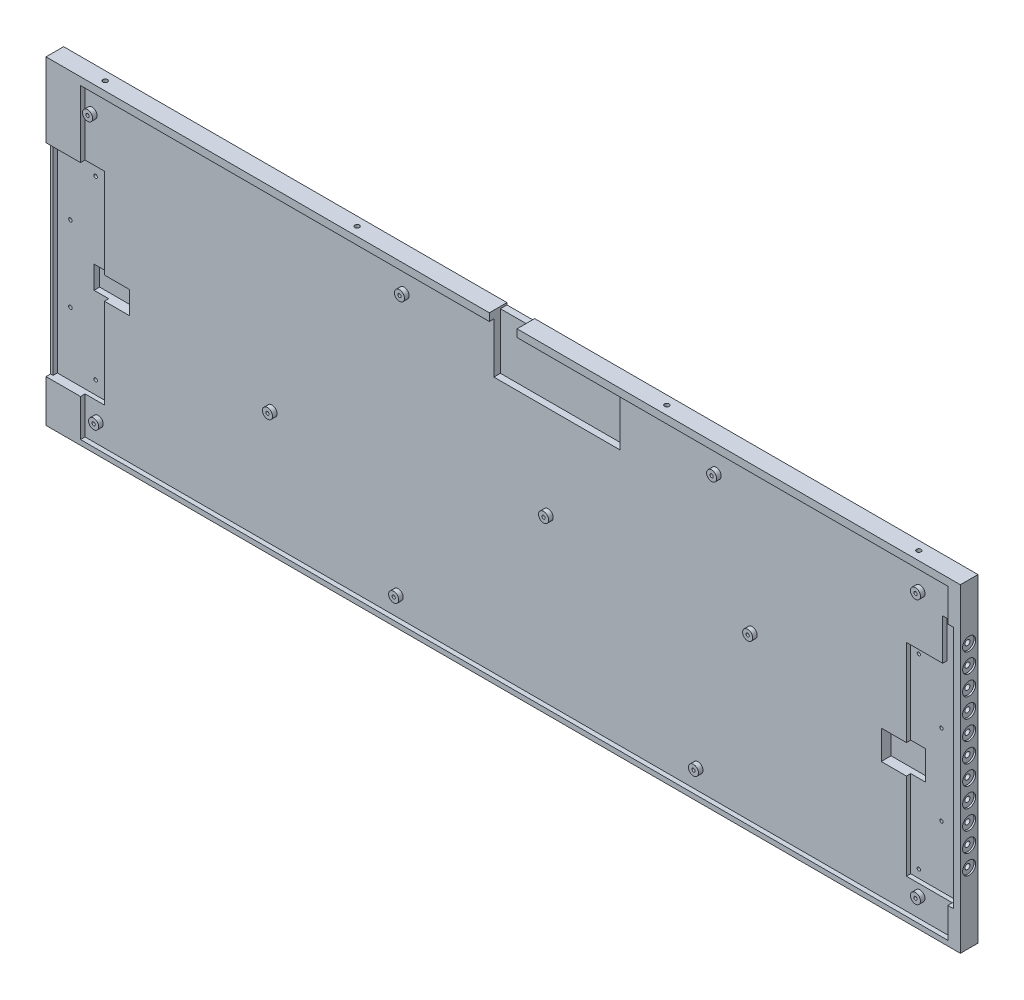
SolidWorks part; units mm, degrees
ref_plane "前视基准面" through (0, 0, 0) normal (0, 0, 1) x (1, 0, 0)
ref_plane "上视基准面" through (0, 0, 0) normal (0, 1, 0) x (1, 0, 0)
ref_plane "右视基准面" through (0, 0, 0) normal (1, 0, 0) x (0, 0, -1)
other "Configuration Table"
sketch "草图1" plane through (0, 0, 0) normal (0, 0, 1) x (1, 0, 0)
  line L1 (0, 0) -> (348.235, 0)
  line L2 (0, 0) -> (0, -124.71)
  line L3 (0, -124.71) -> (348.235, -124.71)
  line L4 (348.235, 0) -> (348.235, -124.71)
  dimension "D1" = 348.235
  dimension "D2" = 124.71
extrude "凸台-拉伸1" add sketch "草图1" along normal blind 7
sketch "草图2" plane through (0, 0, 7) normal (0, 0, 1) x (1, 0, 0)
  line L0 (348.235, 0) -> (0, 0) construction
  line L1 (2, -2) -> (346.235, -2)
  line L2 (2, -2) -> (2, -122.71)
  line L3 (2, -122.71) -> (346.235, -122.71)
  line L4 (346.235, -2) -> (346.235, -122.71)
  line L5 (348.235, -124.71) -> (348.235, 0) construction
  line L6 (0, -124.71) -> (348.235, -124.71) construction
  line L7 (0, 0) -> (0, -124.71) construction
  dimension "D1" = 2
  dimension "D2" = 2
  dimension "D3" = 2
  dimension "D4" = 2
extrude "切除-拉伸1" cut sketch "草图2" against normal blind 1.8
sketch "草图3" plane through (0, 0, 5.2) normal (0, 0, 1) x (1, 0, 0)
  circle A0 centre (4.8, -9.9) radius 2
  circle A1 centre (4.8, -9.9) radius 0.65
  circle A2 centre (7.2, -114.7) radius 2
  circle A3 centre (7.2, -114.7) radius 0.65
  circle A4 centre (76.2, -76.6) radius 2
  circle A5 centre (76.2, -76.6) radius 0.65
  circle A6 centre (128.6, -9.9) radius 2
  circle A7 centre (128.6, -9.9) radius 0.65
  circle A8 centre (126.3, -114.7) radius 2
  circle A9 centre (126.3, -114.7) radius 0.65
  circle A10 centre (185.8, -57.5) radius 2
  circle A11 centre (185.8, -57.5) radius 0.65
  circle A12 centre (252.5, -9.9) radius 2
  circle A13 centre (252.5, -9.9) radius 0.65
  circle A14 centre (245.3, -114.7) radius 2
  circle A15 centre (245.3, -114.7) radius 0.65
  circle A16 centre (333.4, -9.9) radius 2
  circle A17 centre (333.4, -9.9) radius 0.65
  circle A18 centre (333.4, -114.7) radius 2
  circle A19 centre (333.4, -114.7) radius 0.65
  circle A20 centre (266.8, -57.5) radius 2
  circle A21 centre (266.8, -57.5) radius 0.65
  dimension "D1" = 4
  dimension "D2" = 1.3
extrude "凸台-拉伸2" add sketch "草图3" along normal up to surface (1.8 mm away) up to face at (174.1175, -62.355, 7)
sketch "草图4" plane through (0, 0, 5.2) normal (0, 0, 1) x (1, 0, 0)
  line L0 (0, 0) -> (0, -124.71) construction
  line L1 (0, -27.51) -> (9.7, -27.51)
  line L2 (0, -27.51) -> (0, -107.91)
  line L3 (0, -107.91) -> (9.7, -107.91)
  line L4 (9.7, -27.51) -> (9.7, -107.91)
  line L5 (0, -124.71) -> (348.235, -124.71) construction
  dimension "D1" = 80.4
  dimension "D2" = 9.7
  dimension "D3" = 16.8
extrude "切除-拉伸2" cut sketch "草图4" against normal blind 1.7 and the other way through all contours L4 L3 L2 L1
sketch "草图6" plane through (0, 0, 5.2) normal (0, 0, 1) x (1, 0, 0)
  line L5 (3.9, -67.71) -> (9.7, -67.71) construction
  line L6 (3.9, -63.21) -> (19.7, -63.21)
  line L7 (3.9, -63.21) -> (3.9, -72.21)
  line L8 (3.9, -72.21) -> (19.7, -72.21)
  line L9 (19.7, -63.21) -> (19.7, -72.21)
  line L10 (9.7, -27.51) -> (9.7, -107.91) construction
  dimension "D1" = 9
  dimension "D2" = 5.8
  dimension "D3" = 10
extrude "切除-拉伸3" cut sketch "草图6" against normal offset from surface (3.9 mm away) 1.3 up to face at (174.1175, -62.355, 0)
sketch "草图7" plane through (0, 0, 0) normal (-1, 0, 0) x (0, 0, 1)
  line L1 (0, 0) -> (7, 0)
  line L2 (0, 0) -> (0, -27.51)
  line L3 (0, -27.51) -> (7, -27.51)
  line L4 (7, 0) -> (7, -27.51)
  line L5 (7, -107.91) -> (0, -107.91)
  line L6 (7, -107.91) -> (7, -124.71)
  line L7 (7, -124.71) -> (0, -124.71)
  line L8 (0, -107.91) -> (0, -124.71)
  line L9 (0, -107.91) -> (3.5, -107.91)
  line L10 (0, -107.91) -> (0, -27.51)
  line L11 (0, -27.51) -> (3.5, -27.51)
  line L12 (3.5, -107.91) -> (3.5, -27.51)
  line M1 (3.5, -107.91) -> (3.5, -27.51)
  line M2 (3.5, -27.51) -> (7, -27.51)
  line M3 (7, -27.51) -> (7, 0)
  line M4 (7, 0) -> (0, 0)
  line M5 (0, 0) -> (0, -124.71)
  line M6 (0, -124.71) -> (7, -124.71)
  line M7 (7, -124.71) -> (7, -107.91)
  line M8 (7, -107.91) -> (3.5, -107.91)
extrude "凸台-拉伸3" add sketch "草图7" along normal blind 11.7 contours L5 M8 M5 M6 M7 | L5 L3 M1 M5 | L3 M5 M2 M3 M4 region at (0, -13.755, 3.5) region at (0, -67.71, 1.75) region at (0, -116.31, 3.5)
sketch "草图8" plane through (0, 0, 3.5) normal (0, 0, 1) x (1, 0, 0)
  circle A0 centre (-5.5, -82.714) radius 0.7
  circle A1 centre (4.5, -102.714) radius 0.7
  circle A2 centre (-5.5, -52.714) radius 0.7
  circle A3 centre (4.5, -32.714) radius 0.7
  dimension "D1" = 1.4
extrude "切除-拉伸4" cut sketch "草图8" against normal blind 3
sketch "草图9" plane through (0, 0, 3.5) normal (0, 0, 1) x (1, 0, 0)
  line L0 (-11.7, -107.91) -> (2, -107.91) construction
  line L1 (-11.7, -27.51) -> (-10.7, -27.51)
  line L2 (-11.7, -27.51) -> (-11.7, -107.91)
  line L3 (-11.7, -107.91) -> (-10.7, -107.91)
  line L4 (-10.7, -27.51) -> (-10.7, -107.91)
  dimension "D1" = 1
extrude "凸台-拉伸4" add sketch "草图9" along normal up to surface (1.7 mm away) up to face at (64.8892, -65.925, 5.2)
sketch "草图10" plane through (0, 0, 5.2) normal (0, 0, 1) x (1, 0, 0)
  line L1 (328.035, -30.31) -> (348.235, -30.31)
  line L2 (328.035, -30.31) -> (328.035, -110.71)
  line L3 (328.035, -110.71) -> (348.235, -110.71)
  line L4 (348.235, -30.31) -> (348.235, -110.71)
  line L6 (348.235, -124.71) -> (348.235, 0) construction
  line L9 (2, -122.71) -> (346.235, -122.71) construction
  dimension "D1" = 80.4
  dimension "D2" = 20.2
  dimension "D3" = 12
extrude "切除-拉伸5" cut sketch "草图10" against normal blind 1.7 and the other way through all
sketch "草图11" plane through (0, 0, 3.5) normal (0, 0, 1) x (1, 0, 0)
  line L0 (328.035, -70.51) -> (333.835, -70.51) construction
  line L1 (318.035, -64.76) -> (333.835, -64.76)
  line L2 (318.035, -64.76) -> (318.035, -76.26)
  line L3 (318.035, -76.26) -> (333.835, -76.26)
  line L4 (333.835, -64.76) -> (333.835, -76.26)
  line L5 (328.035, -110.71) -> (328.035, -30.31) construction
  dimension "D1" = 11.5
  dimension "D2" = 5.8
  dimension "D3" = 10
extrude "切除-拉伸6" cut sketch "草图11" against normal blind 2.2 and the other way through all
sketch "草图12" plane through (0, 0, 3.5) normal (0, 0, 1) x (1, 0, 0)
  circle A3 centre (331.235, -107.514) radius 0.65
  circle A4 centre (340.235, -86.514) radius 0.65
  circle A5 centre (340.235, -54.514) radius 0.65
  circle A6 centre (331.235, -33.514) radius 0.65
  dimension "D1" = 1.3
extrude "切除-拉伸7" cut sketch "草图12" against normal blind 3
sketch "草图13" plane through (0, 0, 0) normal (0, 0, -1) x (-1, 0, 0)
  line L0 (11.7, -124.71) -> (-348.235, -124.71) construction
  line L1 (-348.235, 0) -> (-351.235, 0)
  line L2 (-348.235, 0) -> (-348.235, -124.71)
  line L3 (-348.235, -124.71) -> (-351.235, -124.71)
  line L4 (-351.235, 0) -> (-351.235, -124.71)
  dimension "D1" = 3
extrude "凸台-拉伸5" add sketch "草图13" against normal up to surface (7 mm away) up to face at (171.1925, -14.955, 7)
sketch "草图14" plane through (0, 0, 5.2) normal (0, 0, 1) x (1, 0, 0)
  line L0 (346.235, -2) -> (2, -2) construction
  line L1 (342.435, -14) -> (348.435, -14)
  line L2 (342.435, -14) -> (342.435, -110.71)
  line L3 (342.435, -110.71) -> (348.435, -110.71)
  line L4 (348.435, -14) -> (348.435, -110.71)
  line L5 (346.235, -110.71) -> (328.035, -110.71) construction
  line L6 (351.235, 0) -> (351.235, -124.71) construction
  dimension "D1" = 12
  dimension "D2" = 6
  dimension "D3" = 2.8
extrude "切除-拉伸8" cut sketch "草图14" against normal up to surface (1.7 mm away) and the other way blind 3 up to face at (340.885, -86.514, 3.5)
sketch "草图15" plane through (351.235, 0, 0) normal (1, 0, 0) x (0, 0, -1)
  line L0 (-7, 0) -> (0, 0) construction
  line L1 (-3.5, -20) -> (-3.5, 0)
  line L2 (-3.5, -104.71) -> (-3.5, -124.71)
  line L4 (-7, -124.71) -> (0, -124.71) construction
  circle A0 centre (-3.5, -20) radius 2.6
  circle A12 centre (-3.5, -20) radius 1
  circle A13 centre (-3.5, -27.7009) radius 2.6
  circle A14 centre (-3.5, -27.7009) radius 1
  circle A15 centre (-3.5, -35.4018) radius 2.6
  circle A16 centre (-3.5, -35.4018) radius 1
  circle A17 centre (-3.5, -43.1027) radius 2.6
  circle A18 centre (-3.5, -43.1027) radius 1
  circle A19 centre (-3.5, -50.8036) radius 2.6
  circle A20 centre (-3.5, -50.8036) radius 1
  circle A21 centre (-3.5, -58.5045) radius 2.6
  circle A22 centre (-3.5, -58.5045) radius 1
  circle A23 centre (-3.5, -66.2055) radius 2.6
  circle A24 centre (-3.5, -66.2055) radius 1
  circle A25 centre (-3.5, -73.9064) radius 2.6
  circle A26 centre (-3.5, -73.9064) radius 1
  circle A27 centre (-3.5, -81.6073) radius 2.6
  circle A28 centre (-3.5, -81.6073) radius 1
  circle A29 centre (-3.5, -89.3082) radius 2.6
  circle A30 centre (-3.5, -89.3082) radius 1
  circle A31 centre (-3.5, -97.0091) radius 2.6
  circle A32 centre (-3.5, -97.0091) radius 1
  circle A33 centre (-3.5, -104.71) radius 2.6
  circle A34 centre (-3.5, -104.71) radius 1
  point P5 (-3.5, 0)
  dimension "D2" = 5.2
  dimension "D3" = 2
  dimension "D1" = 20
  dimension "D4" = 12
extrude "切除-拉伸9" cut sketch "草图15" against normal blind 0.7 contours A0 | A13 | A15 | A17 | A19 | A21 | A23 | A25 | A27 | A29 | A31
extrude "切除-拉伸10" cut sketch "草图15<3>" against normal up to surface (2.8 mm away) contours A12 | A14 | A16 | A18 | A20 | A22 | A24 | A26 | A28 | A30 | A32 up to face at (348.435, -62.355, 5.25)
sketch "草图15<3>" plane through (351.235, 0, 0) normal (1, 0, 0) x (0, 0, -1) same geometry as "草图15"
sketch "草图16" plane through (0, 0, 0) normal (0, 1, 0) x (1, 0, 0)
  line L1 (-11.7, 0) -> (351.235, 0)
  line L2 (-11.7, 0) -> (-11.7, -7)
  line L3 (-11.7, -7) -> (351.235, -7)
  line L4 (351.235, 0) -> (351.235, -7)
extrude "凸台-拉伸6" add sketch "草图16" along normal blind 0.2
sketch "草图17" plane through (0, -124.71, 0) normal (0, -1, 0) x (1, 0, 0)
  line L1 (-11.7, 7) -> (351.235, 7)
  line L2 (-11.7, 7) -> (-11.7, 0)
  line L3 (-11.7, 0) -> (351.235, 0)
  line L4 (351.235, 7) -> (351.235, 0)
extrude "凸台-拉伸7" add sketch "草图17" along normal blind 0.2
sketch "草图23" plane through (0, 0, 0) normal (0, 0, -1) x (-1, 0, 0)
  line L0 (-351.235, 0.2) -> (-351.235, -124.91) construction
  line L1 (11.7, 0.2) -> (11.7, -124.91) construction
  line L2 (-351.235, 0.2) -> (11.7, 0.2) construction
  line L3 (11.7, -124.91) -> (-351.235, -124.91) construction
  circle A0 centre (-331.235, -19.8) radius 5.6
  circle A1 centre (-231.235, -19.8) radius 5.6
  circle A2 centre (-108.3, -19.8) radius 5.6
  circle A3 centre (-8.3, -19.8) radius 5.6
  circle A4 centre (-331.235, -104.91) radius 4.1
  circle A5 centre (-231.235, -104.91) radius 4.1
  circle A6 centre (-108.3, -104.91) radius 4.1
  circle A7 centre (-8.3, -104.91) radius 4.1
  dimension "D1" = 11.2
  dimension "D2" = 8.2
  dimension "D3" = 20
  dimension "D4" = 20
  dimension "D5" = 20
  dimension "D6" = 100
  dimension "D7" = 100
  dimension "D8" = 20
extrude "切除-拉伸14" cut sketch "草图23" against normal blind 1
sketch "草图24" plane through (0, 0.2, 0) normal (0, 1, 0) x (1, 0, 0)
  circle A0 centre (8.3, -3.5) radius 0.9
  circle A1 centre (108.3, -3.5) radius 0.9
  circle A2 centre (231.235, -3.5) radius 0.9
  circle A3 centre (331.235, -3.5) radius 0.9
  dimension "D1" = 1.8
sketch "草图25" plane through (0, 0.2, 0) normal (0, 1, 0) x (1, 0, 0)
  line L1 (-11.7, 0) -> (351.235, 0)
  line L2 (-11.7, 0) -> (-11.7, -7)
  line L3 (-11.7, -7) -> (351.235, -7)
  line L4 (351.235, 0) -> (351.235, -7)
extrude "凸台-拉伸8" add sketch "草图25" along normal blind 1.8
sketch "草图26" plane through (0, 0, 7) normal (0, 0, 1) x (1, 0, 0)
  line L0 (346.235, -14) -> (346.235, -2) construction
  line L1 (2, -2) -> (346.235, -2)
  line L2 (2, -2) -> (2, -1)
  line L3 (2, -1) -> (346.235, -1)
  line L4 (346.235, -2) -> (346.235, -1)
  dimension "D1" = 1
extrude "切除-拉伸15" cut sketch "草图26" against normal up to surface (1.8 mm away) up to face at (268.8, -57.5, 5.2)
sketch "草图27" plane through (0, 2, 0) normal (0, 1, 0) x (1, 0, 0)
  line L0 (351.235, 0) -> (-11.7, 0) construction
  line L1 (164.2675, 0) -> (175.2675, 0)
  line L2 (164.2675, 0) -> (164.2675, -7)
  line L3 (164.2675, -7) -> (175.2675, -7)
  line L4 (175.2675, 0) -> (175.2675, -7)
  line L5 (-11.7, -7) -> (351.235, -7) construction
  line L6 (164.2675, -4) -> (169.7675, -4) construction
  line L7 (169.7675, -4) -> (175.2675, -4) construction
  point P8 (169.7675, -4)
  dimension "D1" = 11
extrude "切除-拉伸16" cut sketch "草图27" against normal blind 0.8
sketch "草图28" plane through (0, 0, 5.2) normal (0, 0, 1) x (1, 0, 0)
  line L0 (346.235, -1) -> (2, -1) construction
  line L1 (164.2675, -1) -> (214.2675, -1)
  line L2 (164.2675, -1) -> (164.2675, -21)
  line L3 (164.2675, -21) -> (214.2675, -21)
  line L4 (214.2675, -1) -> (214.2675, -21)
  line L5 (164.2675, -1) -> (175.2675, -1)
  line L6 (164.2675, -1) -> (164.2675, 1.2)
  line L7 (164.2675, 1.2) -> (175.2675, 1.2)
  line L8 (175.2675, -1) -> (175.2675, 1.2)
  line L9 (164.2675, 1.2) -> (164.2675, 2) construction
  line M21 (346.235, -1) -> (2, -1)
  dimension "D1" = 20
  dimension "D2" = 50
extrude "切除-拉伸17" cut sketch "草图28" against normal blind 2.6 and the other way through all contours L4 L1 L2 L3 M21 | L1 L8 L7 L6 region at (169.7675, 0.1, 5.2) region at (189.2675, -11, 5.2)
sketch "草图29" plane through (-11.7, 0, 0) normal (-1, 0, 0) x (0, 0, 1)
  line L0 (0, 2) -> (0, -124.91) construction
  line L1 (7, -124.91) -> (0, -124.91)
  line L2 (7, -124.91) -> (7, -124.71)
  line L3 (7, -124.71) -> (0, -124.71)
  line L4 (0, -124.91) -> (0, -124.71)
  dimension "D1" = 0.2
extrude "切除-拉伸18" cut sketch "草图29" against normal through all
extrude "切除-拉伸19" cut sketch "草图24" against normal blind 2 from surface starting at face at (76.2837, 2, 3.5)
extrude "切除-拉伸20" cut sketch "草图24<3>" along normal blind 2 from surface starting at face at (169.7675, -124.71, 3.5)
sketch "草图24<3>" plane through (0, 0.2, 0) normal (0, 1, 0) x (1, 0, 0) same geometry as "草图24"
